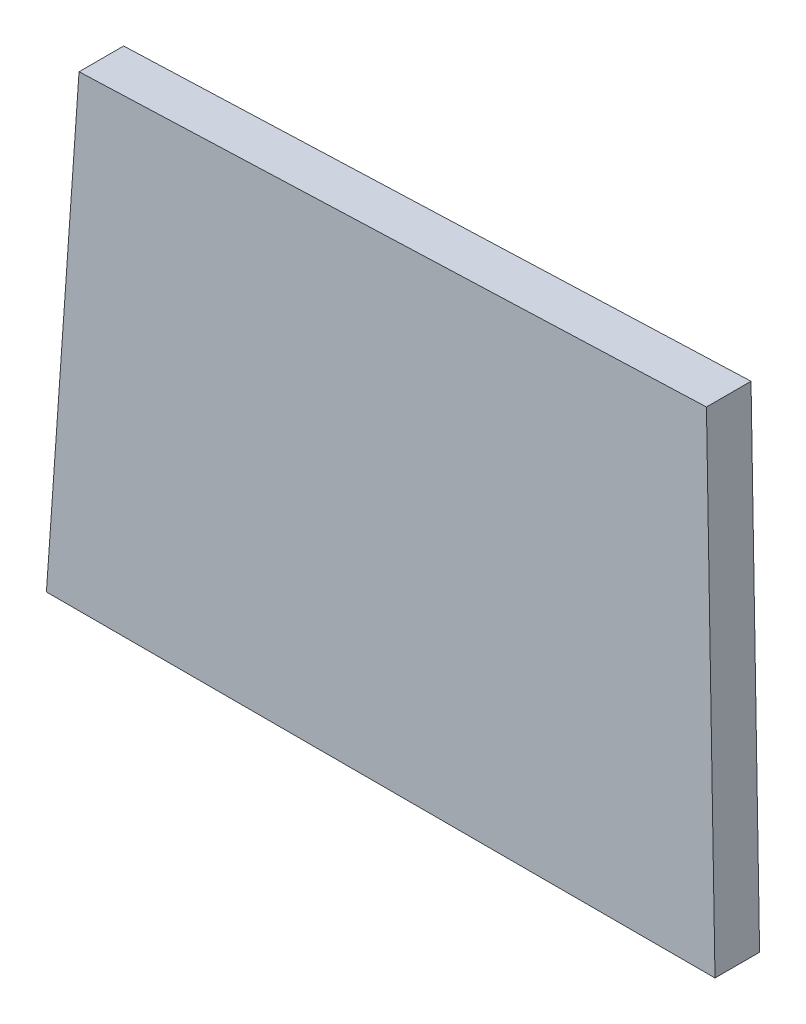
SolidWorks part; units mm, degrees
ref_plane "Ebene vorne" through (0, 0, 0) normal (0, 0, 1) x (1, 0, 0)
ref_plane "Ebene oben" through (0, 0, 0) normal (0, 1, 0) x (1, 0, 0)
ref_plane "Ebene rechts" through (0, 0, 0) normal (1, 0, 0) x (0, 0, -1)
sketch "Skizze1" plane through (0, 0, 0) normal (0, 0, 1) x (1, 0, 0)
  line L0 (0, 0) -> (1.4649, 20.9488)
  line L1 (1.4649, 20.9488) -> (29.616, 21.9966)
  line L2 (29.616, 21.9966) -> (30, 0)
  line L3 (30, 0) -> (0, 0)
  dimension "D1" = 30
  dimension "D2" = 22
  dimension "D3" = 21
  dimension "D4" = 86
  dimension "D5" = 89
extrude "Aufsatz-Linear austragen1" add sketch "Skizze1" along normal blind 2
sketch "Skizze4" plane through (0, 0, 0) normal (0, 0, 1) x (1, 0, 0)
  line L1 (0, 0) -> (30, 0)
  line L2 (0, 0) -> (0, 20)
  line L3 (0, 20) -> (30, 20)
  line L4 (30, 0) -> (30, 20)
  dimension "D1" = 30
  dimension "D2" = 20
sketch "Skizze2" plane through (0, 0, 2) normal (0, 0, 1) x (1, 0, 0)
  circle A0 centre (15.9895, 9.4075) radius 18.5517
sketch "Skizze3" plane through (0, 0, 2) normal (0, 0, 1) x (1, 0, 0)
  line L0 (1.5405, 1.9983) -> (29.5405, 1.9983)
  line L1 (1.5405, 1.9983) -> (1.5405, 19.9983)
  line L2 (29.5405, 1.9983) -> (29.5405, 19.9983)
  line L3 (1.5405, 19.9983) -> (29.5405, 19.9983)
  line L4 (1.5405, 1.9983) -> (29.5405, 19.9983) construction
  line L5 (29.5405, 1.9983) -> (1.5405, 19.9983) construction
  line L6 (30, 0) -> (29.616, 21.9966) construction
  line L7 (29.616, 21.9966) -> (1.4649, 20.9488) construction
  point P1 (15.5405, 10.9983)
  point P8 (29.808, 10.9983)
  point P11 (15.5405, 21.4727)
  dimension "D1" = 18
  dimension "D2" = 28
ref_point "SWASI_Vision_Point_1"
ref_point "SWASI_Vision_Point_1_helper"
ref_point "SWASI_Vision_Point_2"
ref_point "SWASI_Vision_Point_2_helper"
ref_point "SWASI_Vision_Point_3"
ref_point "SWASI_Vision_Point_3_helper"
ref_point "SWASI_Vision_Point_4"
ref_plane "SWASI_Alignment_Plane_1" through (0, 0, 0) normal (0, -1, 0) x (-1, 0, 0)
ref_plane "SWASI_Alignment_Plane_2" through (0, 0, 2) normal (0, 0, -1) x (-1, 0, 0)
ref_axis "Achse3" through (0, 0, 2) along (0.9978, 0, -0.0665)
ref_axis "Achse4" through (0, 0, 0) along (0.9978, 0, 0.0665)
ref_point "SWASI_Surface_Center_Point"
ref_axis "SWASI_Norm_Alignment_Plane_3" through (30, 0, 0) along (-1, 0, 0)
ref_plane "SWASI_Alignment_Plane_3_G" through (15, 0, 1) normal (-1, 0, 0) x (0, 0, 1)
